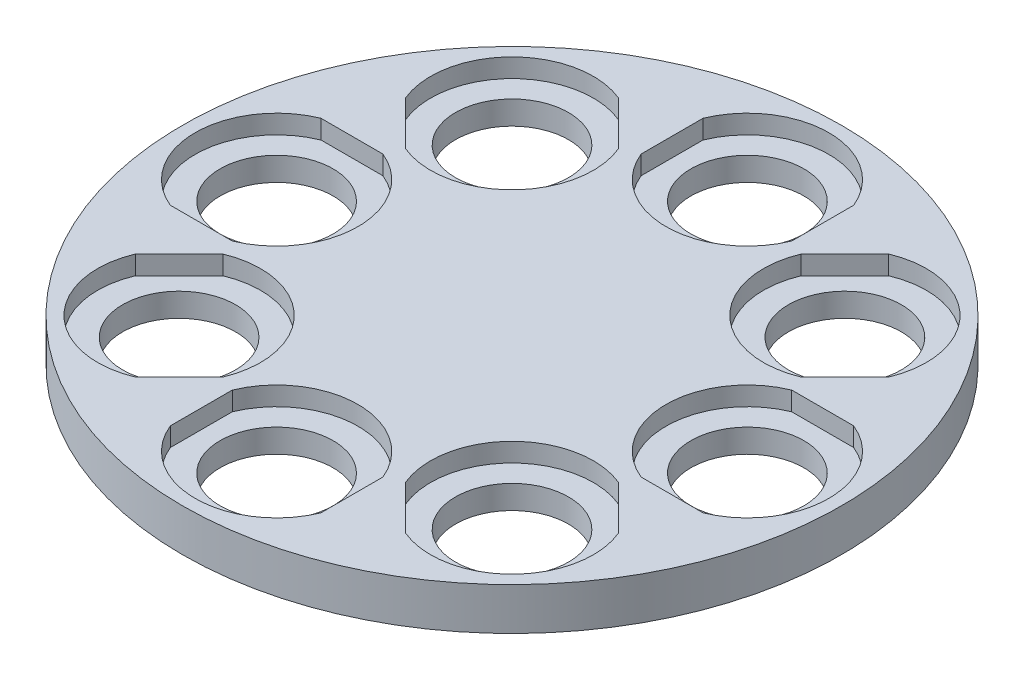
SolidWorks part; units mm, degrees
ref_plane "Front Plane" through (0, 0, 0) normal (0, 0, 1) x (1, 0, 0)
ref_plane "Top Plane" through (0, 0, 0) normal (0, 1, 0) x (1, 0, 0)
ref_plane "Right Plane" through (0, 0, 0) normal (1, 0, 0) x (0, 0, -1)
sketch "Sketch1" plane through (0, 0, 0) normal (0, 1, 0) x (1, 0, 0)
  line L0 (70, 0) -> (50, 0) construction
  circle A0 centre (0, 0) radius 70
  circle A1 centre (50, 0) radius 12
  circle A2 centre (35.3553, -35.3553) radius 12
  circle A3 centre (0, -50) radius 12
  circle A4 centre (-35.3553, -35.3553) radius 12
  circle A5 centre (-50, 0) radius 12
  circle A6 centre (-35.3553, 35.3553) radius 12
  circle A7 centre (0, 50) radius 12
  circle A8 centre (35.3553, 35.3553) radius 12
  point P23 (0, 0)
  dimension "D1" = 140
  dimension "D3" = 24
  dimension "D2" = 20
  dimension "D4" = 8
extrude "Boss-Extrude1" add sketch "Sketch1" along normal blind 25
sketch "Sketch2" plane through (0, 25, 0) normal (0, 1, 0) x (1, 0, 0)
  line L0 (50, 0) -> (50, 16) construction
  line L1 (50, 16) -> (43.4205, 16)
  line L2 (50, 16) -> (56.5795, 16)
  line L3 (32.7, 0) -> (67.3, 0) construction
  line L4 (50, -16) -> (56.5795, -16)
  line L5 (50, -16) -> (43.4205, -16)
  line L6 (46.669, -24.0416) -> (42.0166, -19.3892)
  line L7 (24.0416, -46.669) -> (19.3892, -42.0166)
  line L8 (24.0416, -46.669) -> (28.694, -51.3215)
  line L9 (46.669, -24.0416) -> (51.3215, -28.694)
  line L10 (16, -50) -> (16, -43.4205)
  line L11 (-16, -50) -> (-16, -43.4205)
  line L12 (-16, -50) -> (-16, -56.5795)
  line L13 (16, -50) -> (16, -56.5795)
  line L14 (-24.0416, -46.669) -> (-19.3892, -42.0166)
  line L15 (-46.669, -24.0416) -> (-42.0166, -19.3892)
  line L16 (-46.669, -24.0416) -> (-51.3215, -28.694)
  line L17 (-24.0416, -46.669) -> (-28.694, -51.3215)
  line L18 (-50, -16) -> (-43.4205, -16)
  line L19 (-50, 16) -> (-43.4205, 16)
  line L20 (-50, 16) -> (-56.5795, 16)
  line L21 (-50, -16) -> (-56.5795, -16)
  line L22 (-46.669, 24.0416) -> (-42.0166, 19.3892)
  line L23 (-24.0416, 46.669) -> (-19.3892, 42.0166)
  line L24 (-24.0416, 46.669) -> (-28.694, 51.3215)
  line L25 (-46.669, 24.0416) -> (-51.3215, 28.694)
  line L26 (-16, 50) -> (-16, 43.4205)
  line L27 (16, 50) -> (16, 43.4205)
  line L28 (16, 50) -> (16, 56.5795)
  line L29 (-16, 50) -> (-16, 56.5795)
  line L30 (24.0416, 46.669) -> (19.3892, 42.0166)
  line L31 (46.669, 24.0416) -> (42.0166, 19.3892)
  line L32 (46.669, 24.0416) -> (51.3215, 28.694)
  line L33 (24.0416, 46.669) -> (28.694, 51.3215)
  arc A0 (43.4205, 16) -> (43.4205, -16) centre (50, 0) ccw
  arc A1 (56.5795, -16) -> (56.5795, 16) centre (50, 0) ccw
  arc A2 (42.0166, -19.3892) -> (19.3892, -42.0166) centre (35.3553, -35.3553) ccw
  arc A3 (28.694, -51.3215) -> (51.3215, -28.694) centre (35.3553, -35.3553) ccw
  arc A4 (16, -43.4205) -> (-16, -43.4205) centre (0, -50) ccw
  arc A5 (-16, -56.5795) -> (16, -56.5795) centre (0, -50) ccw
  arc A6 (-19.3892, -42.0166) -> (-42.0166, -19.3892) centre (-35.3553, -35.3553) ccw
  arc A7 (-51.3215, -28.694) -> (-28.694, -51.3215) centre (-35.3553, -35.3553) ccw
  arc A8 (-43.4205, -16) -> (-43.4205, 16) centre (-50, 0) ccw
  arc A9 (-56.5795, 16) -> (-56.5795, -16) centre (-50, 0) ccw
  arc A10 (-42.0166, 19.3892) -> (-19.3892, 42.0166) centre (-35.3553, 35.3553) ccw
  arc A11 (-28.694, 51.3215) -> (-51.3215, 28.694) centre (-35.3553, 35.3553) ccw
  arc A12 (-16, 43.4205) -> (16, 43.4205) centre (0, 50) ccw
  arc A13 (16, 56.5795) -> (-16, 56.5795) centre (0, 50) ccw
  arc A14 (19.3892, 42.0166) -> (42.0166, 19.3892) centre (35.3553, 35.3553) ccw
  arc A15 (51.3215, 28.694) -> (28.694, 51.3215) centre (35.3553, 35.3553) ccw
  point P61 (0, 0)
  dimension "D1" = 34.6
  dimension "D2" = 16
  dimension "D3" = 8
extrude "Cut-Extrude1" cut sketch "Sketch2" against normal blind 10
ref_plane "Plane1" through (0, 10, 0) normal (0, 1, 0) x (1, 0, 0)
split "Split1" trim tools "Plane1" bodies to split 102 resulting bodies 103 104
delete or keep bodies "Body-Delete/Keep 1" type delete bodies bodies 104
sketch "Sketch3" plane through (0, 10, 0) normal (0, -1, 0) x (1, 0, 0)
  circle A0 centre (0, 0) radius 20
  dimension "D1" = 40
extrude "Cut-Extrude2" cut sketch "Sketch3" against normal blind 7.5
sketch "Sketch4" plane through (0, 25, 0) normal (0, 1, 0) x (1, 0, 0)
  circle A0 centre (0, 0) radius 70
extrude "Cut-Extrude3" cut sketch "Sketch4" against normal blind 6
